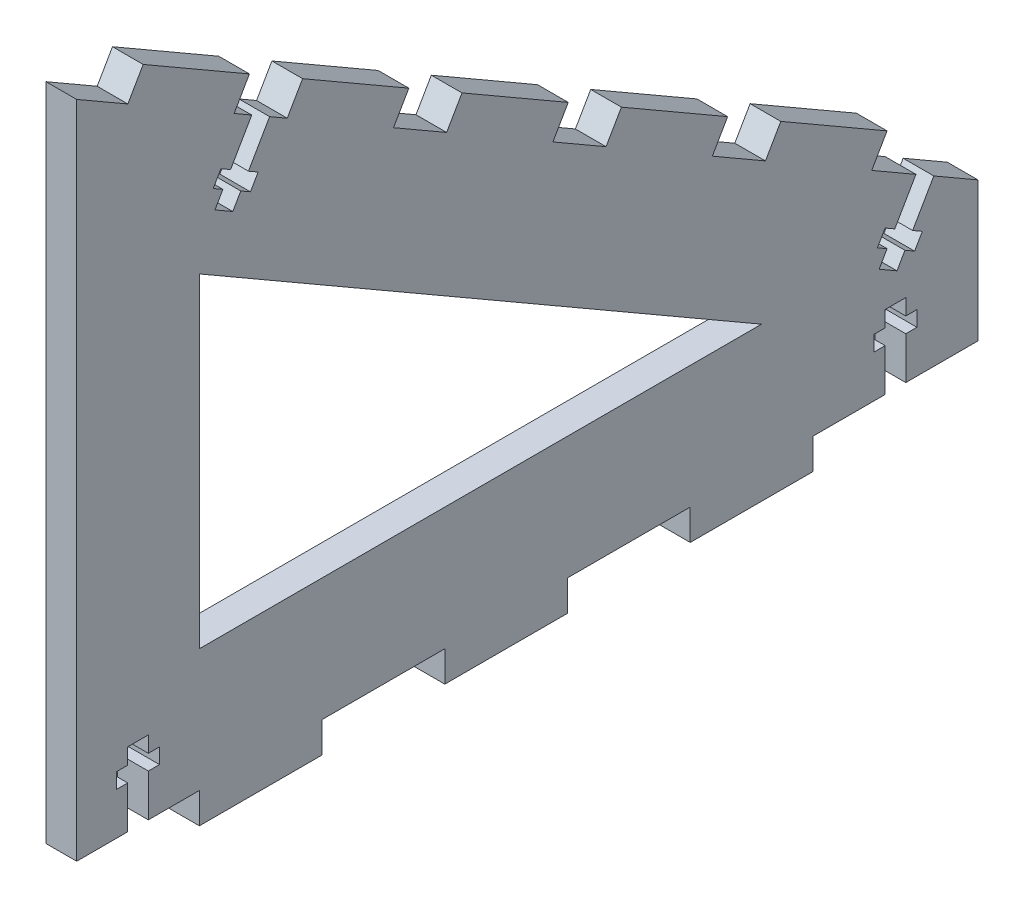
SolidWorks part; units mm, degrees
ref_plane "Front Plane" through (0, 0, 0) normal (0, 0, 1) x (1, 0, 0)
ref_plane "Top Plane" through (0, 0, 0) normal (0, 1, 0) x (1, 0, 0)
ref_plane "Right Plane" through (0, 0, 0) normal (1, 0, 0) x (0, 0, -1)
sketch "Sketch1" plane through (-32.0384, 0, 0) normal (-1, 0, 0) x (0, 0, 1)
  line L0 (-215.9, 95.25) -> (-215.9, 124.1125)
  line L1 (165.3114, 95.25) -> (152.9655, 95.25) construction
  line L2 (-215.9, 124.1125) -> (-29.3333, 231.8268)
  line L3 (-29.3333, 231.8268) -> (-29.3333, 95.25)
  line L4 (-29.3333, 95.25) -> (-215.9, 95.25)
  line L5 (-29.3333, 231.8268) -> (-42.2787, 224.3528) construction
  line L6 (-29.3333, 95.25) -> (-29.3333, 231.8268) construction
extrude "Boss-Extrude1" add sketch "Sketch1" along normal mid plane 6.35
sketch "Sketch2" plane through (-35.2134, 0, 0) normal (-1, 0, 0) x (0, 0, 1)
  line L14 (-54.7333, 120.65) -> (-54.7333, 187.8327)
  line L15 (-171.0972, 120.65) -> (-54.7333, 120.65)
  line L16 (-54.7333, 187.8327) -> (-171.0972, 120.65)
  line L17 (-54.7333, 120.65) -> (-54.7333, 187.8327)
  line L18 (-171.0972, 120.65) -> (-54.7333, 120.65)
  line L19 (-54.7333, 187.8327) -> (-171.0972, 120.65)
  dimension "D1" = 25.4
extrude "Cut-Extrude1" cut sketch "Sketch2" against normal blind 6.35
sketch "Sketch3" plane through (0, 186.5718, -107.7173) normal (0, 0.866, -0.5) x (1, 0, 0)
  line L0 (-35.2134, -90.51) -> (-35.2134, 124.9186) construction
  line L1 (-35.2134, 99.5186) -> (-28.8634, 99.5186)
  line L2 (-35.2134, 99.5186) -> (-35.2134, 74.1186)
  line L3 (-35.2134, 74.1186) -> (-28.8634, 74.1186)
  line L4 (-28.8634, 99.5186) -> (-28.8634, 74.1186)
  line L5 (-28.8634, -90.51) -> (-28.8634, 124.9186) construction
  dimension "D1" = 25.4
  dimension "D2" = 25.4
extrude "Boss-Extrude2" add sketch "Sketch3" along normal blind 6.35
pattern_linear "LPattern1" count 5 spacing 38.1 along (0, 0.5, 0.866) of "Boss-Extrude2"
sketch "Sketch4" plane through (0, 95.25, 0) normal (0, -1, 0) x (1, 0, 0)
  line L0 (-35.2134, -215.9) -> (-35.2134, -29.3333) construction
  line L1 (-35.2134, -54.7333) -> (-28.8634, -54.7333)
  line L2 (-35.2134, -54.7333) -> (-35.2134, -80.1333)
  line L3 (-35.2134, -80.1333) -> (-28.8634, -80.1333)
  line L4 (-28.8634, -54.7333) -> (-28.8634, -80.1333)
  line L5 (-28.8634, -215.9) -> (-28.8634, -29.3333) construction
  dimension "D1" = 25.4
  dimension "D2" = 25.4
extrude "Boss-Extrude3" add sketch "Sketch4" along normal blind 6.35
pattern_linear "LPattern2" count 3 spacing 50.8 along (0, 0, -1) of "Boss-Extrude3"
sketch "Sketch5" plane through (-28.8634, 0, 0) normal (1, 0, 0) x (0, 0, -1)
  line L0 (174.6668, 95.25) -> (170.6832, 95.25) construction
  line L1 (198.8167, 95.25) -> (198.8167, 119.6237) construction
  line L2 (215.9, 95.25) -> (181.7333, 95.25) construction
  line L3 (42.0333, 95.25) -> (42.0333, 127.2639) construction
  line L4 (54.7333, 95.25) -> (29.3333, 95.25) construction
  line L5 (-152.9655, 95.25) -> (-165.3114, 95.25) construction
  line B0 (196.6831, 95.25) -> (200.9503, 95.25)
  line B1 (200.9503, 107.188) -> (203.2617, 107.188)
  line B2 (203.2617, 107.188) -> (203.2617, 104.013)
  line B3 (203.2617, 104.013) -> (200.9503, 104.013)
  line B4 (200.9503, 104.013) -> (200.9503, 95.25)
  line B5 (200.9503, 107.188) -> (200.9503, 110.49)
  line B6 (200.9503, 110.49) -> (196.6831, 110.49)
  line B7 (196.6831, 107.188) -> (196.6831, 110.49)
  line B8 (196.6831, 104.013) -> (196.6831, 95.25)
  line B9 (194.3717, 104.013) -> (196.6831, 104.013)
  line B10 (194.3717, 107.188) -> (194.3717, 104.013)
  line B11 (196.6831, 107.188) -> (194.3717, 107.188)
  line B12 (39.8997, 95.25) -> (44.1669, 95.25)
  line B13 (44.1669, 107.188) -> (46.4783, 107.188)
  line B14 (46.4783, 107.188) -> (46.4783, 104.013)
  line B15 (46.4783, 104.013) -> (44.1669, 104.013)
  line B16 (44.1669, 104.013) -> (44.1669, 95.25)
  line B17 (44.1669, 107.188) -> (44.1669, 110.49)
  line B18 (44.1669, 110.49) -> (39.8997, 110.49)
  line B19 (39.8997, 107.188) -> (39.8997, 110.49)
  line B20 (39.8997, 104.013) -> (39.8997, 95.25)
  line B21 (37.5883, 104.013) -> (39.8997, 104.013)
  line B22 (37.5883, 107.188) -> (37.5883, 104.013)
  line B23 (39.8997, 107.188) -> (37.5883, 107.188)
sketch_block_instance "TSlot-1"
sketch_block "TSlot" parameters "D1"=3.302, "D2"=3.175
sketch_block_instance "TSlot-3"
extrude "Cut-Extrude2" cut sketch "Sketch5" against normal blind 6.35
sketch "Sketch6" plane through (-28.8634, 0, 0) normal (1, 0, 0) x (0, 0, -1)
  line L1 (51.3304, 219.1268) -> (73.3274, 206.4268) construction
  line L3 (183.3127, 142.9268) -> (205.3097, 130.2268) construction
  line L4 (204.9015, 130.4625) -> (196.0314, 115.099) construction
  line L5 (193.903, 136.8125) -> (215.9, 124.1125) construction
  line L6 (67.4199, 209.8375) -> (60.3001, 197.5056) construction
  line L7 (61.9207, 213.0125) -> (72.9192, 206.6625) construction
  line B0 (206.7492, 129.3957) -> (203.0537, 131.5293)
  line B1 (197.0847, 121.1907) -> (195.083, 122.3464)
  line B2 (195.083, 122.3464) -> (196.6705, 125.096)
  line B3 (196.6705, 125.096) -> (198.6722, 123.9403)
  line B4 (198.6722, 123.9403) -> (203.0537, 131.5293)
  line B5 (197.0847, 121.1907) -> (195.4337, 118.3311)
  line B6 (195.4337, 118.3311) -> (199.1292, 116.1975)
  line B7 (200.7802, 119.0571) -> (199.1292, 116.1975)
  line B8 (202.3677, 121.8067) -> (206.7492, 129.3957)
  line B9 (204.3695, 120.651) -> (202.3677, 121.8067)
  line B10 (202.782, 117.9014) -> (204.3695, 120.651)
  line B11 (200.7802, 119.0571) -> (202.782, 117.9014)
  line B12 (69.2677, 208.7707) -> (65.5722, 210.9043)
  line B13 (59.6032, 200.5657) -> (57.6015, 201.7214)
  line B14 (57.6015, 201.7214) -> (59.189, 204.471)
  line B15 (59.189, 204.471) -> (61.1907, 203.3153)
  line B16 (61.1907, 203.3153) -> (65.5722, 210.9043)
  line B17 (59.6032, 200.5657) -> (57.9522, 197.7061)
  line B18 (57.9522, 197.7061) -> (61.6477, 195.5725)
  line B19 (63.2987, 198.4321) -> (61.6477, 195.5725)
  line B20 (64.8862, 201.1817) -> (69.2677, 208.7707)
  line B21 (66.8879, 200.026) -> (64.8862, 201.1817)
  line B22 (65.3004, 197.2764) -> (66.8879, 200.026)
  line B23 (63.2987, 198.4321) -> (65.3004, 197.2764)
sketch_block_instance "TSlot-4"
sketch_block_instance "TSlot-5"
extrude "Cut-Extrude3" cut sketch "Sketch6" against normal blind 6.35
